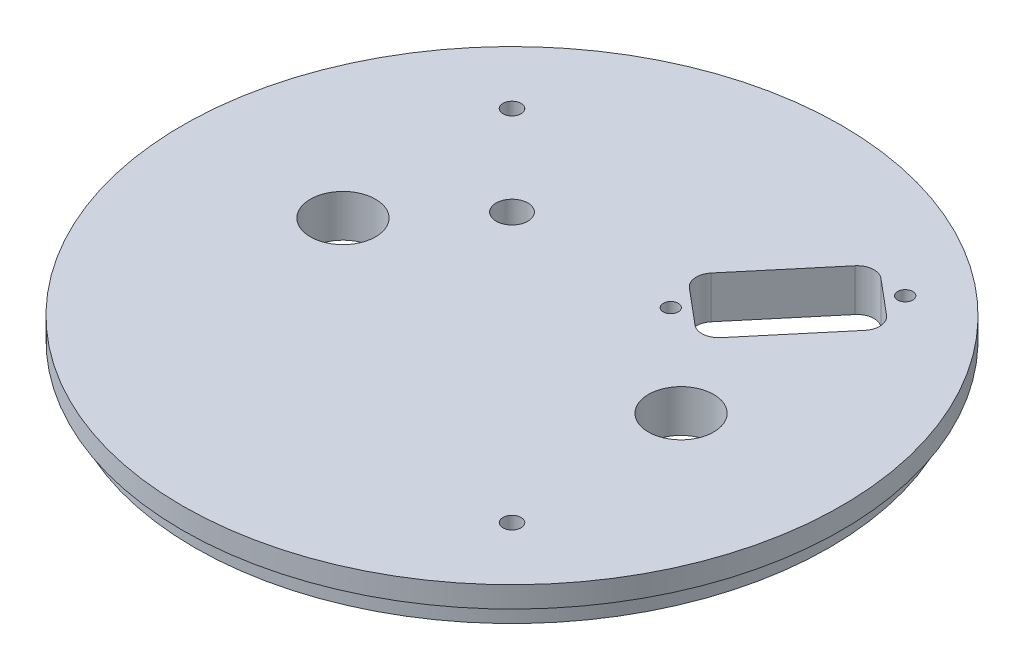
SolidWorks part; units mm, degrees
material "6061-T6 (SS)"
ref_plane "Front Plane" through (0, 0, 0) normal (0, 0, 1) x (1, 0, 0)
ref_plane "Top Plane" through (0, 0, 0) normal (0, 1, 0) x (1, 0, 0)
ref_plane "Right Plane" through (0, 0, 0) normal (1, 0, 0) x (0, 0, -1)
sketch "Sketch1" plane through (0, 0, 0) normal (0, 1, 0) x (1, 0, 0)
  line L0 (0, -49.5173) -> (0, 49.5173) construction
  line L1 (-49.5173, 0) -> (49.5173, 0) construction
  line L2 (-26.9408, 26.9408) -> (0, 0) construction
  line L3 (0, 56.7387) -> (0, 29.6936) construction
  line L4 (3.6407, 56.7387) -> (3.6407, 29.6936) construction
  line L5 (-3.6407, 56.7387) -> (-3.6407, 29.6936) construction
  line L6 (0, -56.7387) -> (0, -29.6936) construction
  line L7 (3.6407, -56.7387) -> (3.6407, -29.6936) construction
  line L8 (-3.6407, -56.7387) -> (-3.6407, -29.6936) construction
  line L9 (-35.014, -35.014) -> (54.3236, 54.3236) construction
  circle A0 centre (0, 0) radius 49.5173
  circle A1 centre (0, 0) radius 3.175 construction
  circle A2 centre (25.4, 0) radius 4.9022
  circle A3 centre (-25.4, 0) radius 4.9022
  circle A4 centre (-26.9408, 26.9408) radius 1.3589
  arc A6 (3.6407, 56.7387) -> (-3.6407, 56.7387) centre (0, 56.7387) ccw construction
  arc A7 (-3.6407, 29.6936) -> (3.6407, 29.6936) centre (0, 29.6936) ccw construction
  arc A8 (3.6407, -56.7387) -> (-3.6407, -56.7387) centre (0, -56.7387) cw construction
  arc A9 (-3.6407, -29.6936) -> (3.6407, -29.6936) centre (0, -29.6936) cw construction
  circle A10 centre (26.9408, -26.9408) radius 1.3589
  circle A11 centre (-13.4704, 13.4704) radius 2.3813
  circle A12 centre (13.4704, -13.4704) radius 2.3813 construction
  point P16 (0, 43.2162)
  point P19 (0, 0)
  point P26 (0, -43.2162)
  dimension "D1" = 99.0346
  dimension "D2" = 6.35
  dimension "D3" = 9.8044
  dimension "D5" = 2.7178
  dimension "D8" = 4.7625
  dimension "D6" = 38.1
  dimension "D7" = 45
  dimension "D4" = 45
  dimension "D9" = 25.4
extrude "Boss-Extrude1" add sketch "Sketch1" along normal blind 6.35
sketch "Sketch2" plane through (0, 0, 0) normal (0, -1, 0) x (1, 0, 0)
  circle A0 centre (0, 0) radius 49.5173
  circle A1 centre (0, 0) radius 47.6885
  dimension "D1" = 99.0346
  dimension "D2" = 95.377
extrude "Cut-Extrude1" cut sketch "Sketch2" against normal blind 3.175
sketch "Sketch3" plane through (0, 6.35, 0) normal (0, 1, 0) x (1, 0, 0)
  line L0 (0, 49.5173) -> (0, -49.5173) construction
  line L1 (-49.5173, 0) -> (49.5173, 0) construction
  line L2 (0, 34.925) -> (0, 13.335) construction
  line L3 (3.2385, 34.925) -> (3.2385, 13.335)
  line L4 (-3.2385, 34.925) -> (-3.2385, 13.335)
  line L5 (0, -34.925) -> (0, -13.335) construction
  line L6 (3.2385, -34.925) -> (3.2385, -13.335)
  line L7 (-3.2385, -34.925) -> (-3.2385, -13.335)
  circle A0 centre (0, 0) radius 49.5173 construction
  arc A1 (3.2385, 34.925) -> (-3.2385, 34.925) centre (0, 34.925) ccw
  arc A2 (-3.2385, 13.335) -> (3.2385, 13.335) centre (0, 13.335) ccw
  arc A3 (3.2385, -34.925) -> (-3.2385, -34.925) centre (0, -34.925) cw
  arc A4 (-3.2385, -13.335) -> (3.2385, -13.335) centre (0, -13.335) cw
  point P7 (0, 13.335)
  point P8 (0, 34.925)
  point P12 (0, 24.13)
  point P20 (0, -24.13)
  point P25 (0, -34.925)
  point P26 (0, -13.335)
  dimension "D1" = 13.335
  dimension "D2" = 34.925
  dimension "D3" = 6.477
extrude "Cut-Extrude2" cut sketch "Sketch3" against normal blind 3.556 from offset 5.969 offset against normal yes
hole_wizard "Tap Drill for #4-40 Tap1" positions "Sketch5" profile "Sketch6" hole size "#4-40" standard "ANSI Inch" end condition through all
sketch "Sketch5" plane through (0, 6.35, 0) normal (0, 1, 0) x (1, 0, 0)
  line L0 (0, 0) -> (53.6567, 63.9455) construction
  line L2 (0, 0) -> (25.4, 0) construction
  point P0 (10.8845, 12.9717)
  point P2 (26.9542, 32.1228)
  dimension "D1" = 50
  dimension "D2" = 25
  dimension "D3" = 16.9333
sketch "Sketch6" plane through (10.8845, 6.35, -12.9717) normal (1, 0, 0) x (0, 0, 1)
  line L0 (0, 0) -> (0, 6.35)
  line L1 (0, 6.35) -> (1.1303, 6.35)
  line L2 (1.1303, 6.35) -> (1.1303, 0)
  line L5 (1.1303, 0) -> (0, 0)
  line L11 (0, -6.35) -> (0, 107.95) construction
  dimension "Thru Hole Dia." = 2.2606
  dimension "Thru Hole Depth" = 6.35
sketch "Sketch4" plane through (0, 6.35, 0) normal (0, 1, 0) x (1, 0, 0)
  line L0 (9.7272, 16.927) -> (14.9807, 12.5187)
  line L1 (9.4141, 20.5054) -> (19.2796, 32.2627)
  line L2 (18.5591, 12.8318) -> (28.4247, 24.5891)
  line L3 (22.858, 32.5757) -> (28.1116, 28.1675)
  line L4 (0, 0) -> (26.9542, 32.1228) construction
  circle A1 centre (10.8845, 12.9717) radius 1.1303 construction
  arc A2 (19.2796, 32.2627) -> (22.858, 32.5757) centre (21.2254, 30.63) cw
  arc A3 (28.4247, 24.5891) -> (28.1116, 28.1675) centre (26.4789, 26.2217) ccw
  arc A4 (14.9807, 12.5187) -> (18.5591, 12.8318) centre (16.6134, 14.4645) ccw
  arc A5 (9.4141, 20.5054) -> (9.7272, 16.927) centre (11.3599, 18.8727) ccw
  point P11 (12.3539, 14.7229)
  dimension "D4" = 2.54
  dimension "D1" = 2.286
  dimension "D2" = 2.286
  dimension "D3" = 11.938
extrude "Cut-Extrude3" cut sketch "Sketch4" against normal through all
equation "\"leadDist\"= \"Lead_Screw_Dist\""
equation "\"Lead_Screw_Dist\" = 2in"
equation "\"D9@Sketch1\"=\"Lead_Screw_Dist\"/2"
equation "\"Lead_Screw_Diam\" = 0.375in"
equation "\"D3@Sketch1\"=\"Lead_Screw_Hole_Diam\""
equation "\"DB9_Hole_Dist\"= 25mm"
equation "\"Airbrakes_Wire_Hole_Dia\"= .25in"
equation "\"Mid_Coupler_Length\"= 13in"
equation "\"D2@Sketch5\"=\"DB9_Hole_Dist\""
equation "\"DB9_Relief_Width\"= 0.47in"
equation "\"DB9_Relief_Hole_Offset\"= 0.09in"
equation "\"D1@Sketch4\"=\"DB9_Relief_Hole_Offset\""
equation "\"D2@Sketch4\"=\"DB9_Relief_Hole_Offset\""
equation "\"D3@Sketch4\"=\"DB9_Relief_Width\""
equation "\"Body_Tube_OD\"= 4.024in"
equation "\"Body_Tube_ID\"= 3.90in"
equation "\"Coupler_OD\" = 3.899in"
equation "\"Coupler_ID\" = 3.755in"
equation "\"Avionics_Bulkhead_Thickness\" = 0.25in"
equation "\"Avionics_Bulkhead_Lip\" = 0.125in"
equation "\"Lead_Screw_Hole_Diam\" = 0.386in"
equation "\"Lead_Screw_Length\" = \"Mid_Coupler_Length\" + 2*0.375in + 2*0.5in"
equation "\"D1@Sketch1\"=\"Coupler_OD\""
equation "\"D1@Sketch2\"=\"Coupler_OD\""
equation "\"D1@Cut-Extrude1\"=\"Avionics_Bulkhead_Lip\""
equation "\"D1@Boss-Extrude1\"=\"Avionics_Bulkhead_Thickness\""
equation "\"D2@Sketch2\"=\"Coupler_ID\""
